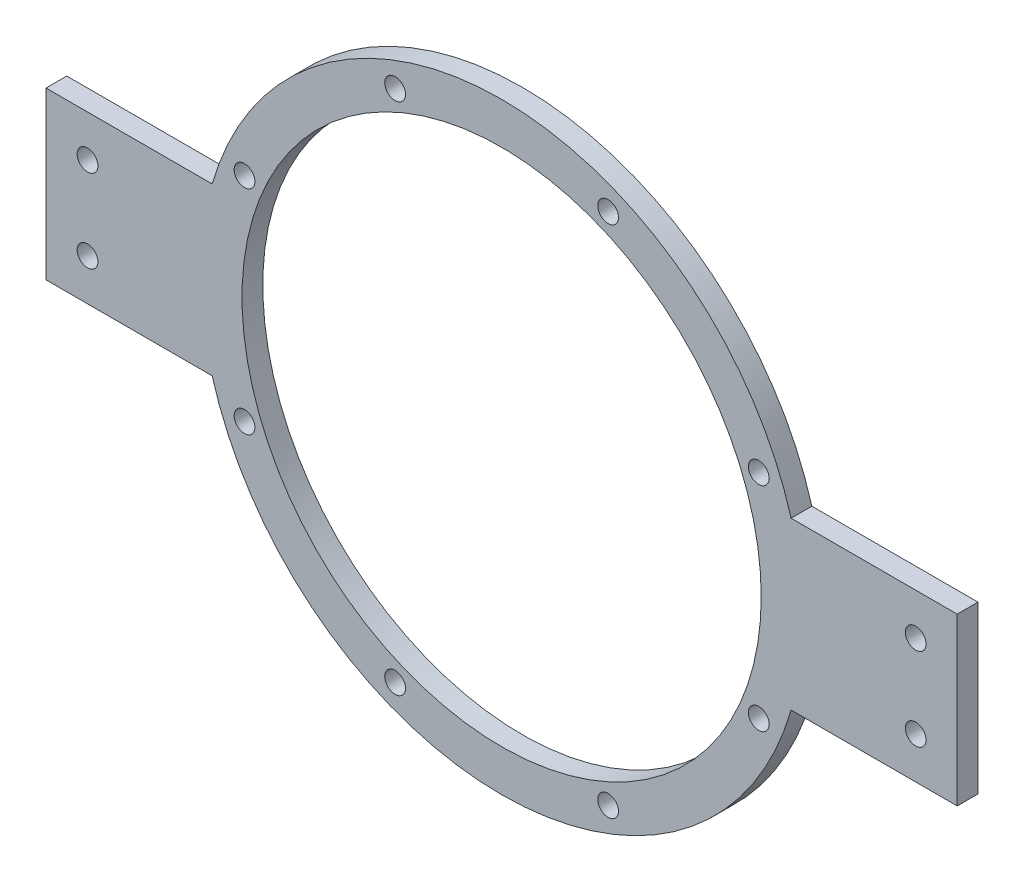
SolidWorks part; units mm, degrees
ref_plane "Front Plane" through (0, 0, 0) normal (0, 0, 1) x (1, 0, 0)
ref_plane "Top Plane" through (0, 0, 0) normal (0, 1, 0) x (1, 0, 0)
ref_plane "Right Plane" through (0, 0, 0) normal (1, 0, 0) x (0, 0, -1)
sketch "Sketch1" plane through (0, 0, 0) normal (0, 0, 1) x (1, 0, 0)
  line L0 (-139.3022, 25.4) -> (-88.5022, 25.4)
  line L1 (-139.3022, -25.4) -> (-88.5022, -25.4)
  line L2 (139.3022, 25.4) -> (88.5022, 25.4)
  line L3 (139.3022, -25.4) -> (88.5022, -25.4)
  line L4 (-139.3022, 25.4) -> (-139.3022, -25.4)
  line L5 (139.3022, 25.4) -> (139.3022, -25.4)
  circle A0 centre (0, 0) radius 79.375
  arc A1 (-88.5022, -25.4) -> (88.5022, -25.4) centre (0, 0) ccw
  arc A2 (88.5022, 25.4) -> (-88.5022, 25.4) centre (0, 0) ccw
  dimension "D1" = 158.75
  dimension "D2" = 92.075
  dimension "D3" = 50.8
  dimension "D4" = 50.8
extrude "Boss-Extrude1" add sketch "Sketch1" along normal blind 6.35
sketch "Sketch2" plane through (0, 0, 6.35) normal (0, 0, 1) x (1, 0, 0)
  line L0 (-32.5625, 78.6129) -> (32.5625, -78.6129) construction
  line L1 (-78.6129, 32.5625) -> (-78.6129, -32.5625) construction
  line L2 (-88.5022, 25.4) -> (-139.3022, 25.4) construction
  line L3 (-139.3022, 25.4) -> (-139.3022, -25.4) construction
  line L4 (-139.3022, -25.4) -> (-88.5022, -25.4) construction
  line L5 (139.3022, -25.4) -> (139.3022, 25.4) construction
  line L6 (139.3022, 25.4) -> (88.5022, 25.4) construction
  line L7 (88.5022, -25.4) -> (139.3022, -25.4) construction
  circle A0 centre (-32.5625, 78.6129) radius 3.175
  circle A1 centre (32.5625, 78.6129) radius 3.175
  circle A2 centre (78.6129, 32.5625) radius 3.175
  circle A3 centre (78.6129, -32.5625) radius 3.175
  circle A4 centre (32.5625, -78.6129) radius 3.175
  circle A5 centre (-32.5625, -78.6129) radius 3.175
  circle A6 centre (-78.6129, -32.5625) radius 3.175
  circle A7 centre (-78.6129, 32.5625) radius 3.175
  circle A8 centre (-126.6022, 12.7) radius 3.175
  circle A9 centre (-126.6022, -12.7) radius 3.175
  circle A10 centre (126.6022, 12.7) radius 3.175
  circle A11 centre (126.6022, -12.7) radius 3.175
  point P21 (0, 0)
  point P38 (0, 0)
  dimension "D2" = 6.35
  dimension "D4" = 12.7
  dimension "D5" = 12.7
  dimension "D6" = 12.7
  dimension "D7" = 12.7
  dimension "D8" = 12.7
  dimension "D9" = 12.7
  dimension "D10" = 12.7
  dimension "D11" = 6.35
  dimension "D12" = 12.7
  dimension "D1" = 170.18
  dimension "D3" = 8
extrude "Cut-Extrude1" cut sketch "Sketch2" against normal blind 76.2 contours A9 | A6 | A3 | A10 | A11 | A2 | A1 | A8 | A5 | A4 | A0 | A7 region at (32.5625, 78.6129, 6.35) region at (78.6129, 32.5625, 6.35) region at (78.6129, -32.5625, 6.35) region at (-78.6129, -32.5625, 6.35) region at (-126.6022, -12.7, 6.35) region at (126.6022, 12.7, 6.35) region at (126.6022, -12.7, 6.35)
